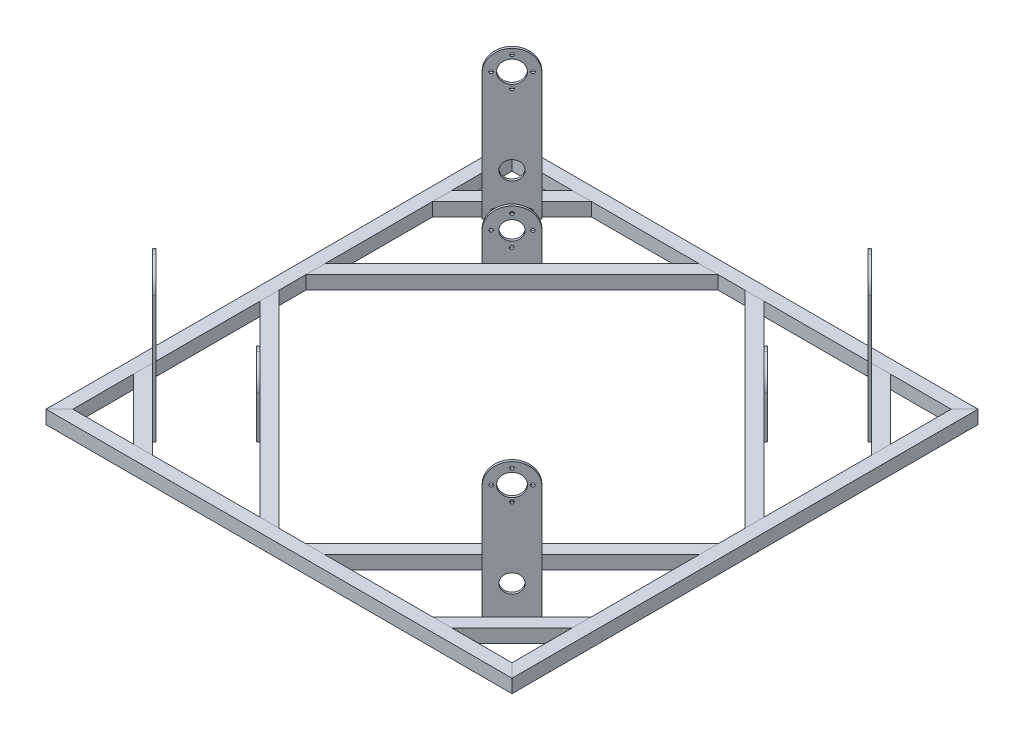
SolidWorks part; units mm, degrees
note: '?' marks a value the reader was unsure of.
material "Alumina"
material "Alumina"
material "Alumina"
material "Plain Carbon Steel"
ref_plane "Front Plane" through (0, 0, 0) normal (0, 0, 1) x (1, 0, 0)
ref_plane "Top Plane" through (0, 0, 0) normal (0, 1, 0) x (1, 0, 0)
ref_plane "Right Plane" through (0, 0, 0) normal (1, 0, 0) x (0, 0, -1)
sketch "Sketch1" plane through (0, 0, 0) normal (0, 1, 0) x (1, 0, 0)
  line L0 (0, 390) -> (0, -390) construction
  line L1 (-390, 0) -> (390, 0) construction
  circle A0 centre (0, 0) radius 390 construction
  dimension "D1" = 780
sketch3d "sketch_profile_base"
  line L0 (-149.9066, 0, 275.7716) -> (-275.7716, 0, 149.9066)
  line L1 (-275.7716, 0, -275.7716) -> (-275.7716, 0, 275.7716)
  line L2 (-275.7716, 0, -275.7716) -> (275.7716, 0, -275.7716)
  line L3 (275.7716, 0, -275.7716) -> (275.7716, 0, 275.7716)
  line L4 (-275.7716, 0, 275.7716) -> (275.7716, 0, 275.7716)
  line L5 (-275.7716, 0, -275.7716) -> (275.7716, 0, 275.7716) construction
  line L6 (275.7716, 0, -275.7716) -> (-275.7716, 0, 275.7716) construction
  line L7 (0, 0, 275.7716) -> (-275.7716, 0, 0)
  line L8 (-390, 0, 0) -> (390, 0, 0) construction
  circle A0 centre (0, 0, 0) radius 390 construction
  point P0 (0, 0, 0)
  point P8 (0, 390, 0)
  dimension "D1" = 45
  dimension "D3" = 106
other "profile_base" corner treatment miter
ref_plane "Plane1" through (-267.8341, 7.9375, -275.7716) normal (0, 0, 1) x (1, 0, 0)
sketch "Sketch12" plane through (-267.8341, 7.9375, -275.7716) normal (0, 0, 1) x (1, 0, 0)
  line L0 (-5.9375, -5.9375) -> (5.9375, -5.9375)
  line L1 (-5.9375, -5.9375) -> (-5.9375, 5.9375)
  line L2 (7.9375, 7.9375) -> (-7.9375, 7.9375)
  line L3 (5.9375, 5.9375) -> (5.9375, -5.9375)
  line L4 (-5.9375, 5.9375) -> (5.9375, 5.9375)
  line L5 (-7.9375, -7.9375) -> (-7.9375, 7.9375)
  line L6 (-7.9375, -7.9375) -> (7.9375, -7.9375)
  line L7 (7.9375, 7.9375) -> (7.9375, -7.9375)
  line L8 (0, -7.9375) -> (0, 7.9375) construction
  line L9 (0, 7.9375) -> (0, -5.9375) construction
  line L10 (0, -5.9375) -> (0, 5.9375) construction
  line L11 (-7.9375, 0) -> (-5.9375, 0) construction
  line L12 (-5.9375, 0) -> (5.9375, 0) construction
  line L13 (5.9375, 0) -> (7.9375, 0) construction
  point P6 (-7.9375, -7.9375)
  point P33 (7.9375, -7.9375)
  point P35 (-7.9375, 5.9375)
  point P36 (7.9375, 5.9375)
  point P37 (0, 0)
  point P38 (0, 0)
  dimension "D1" = 15.875
  dimension "D2" = 15.875
  dimension "D3" = 2
  dimension "D4" = 2
sketch "Sketch14" plane through (-212.8391, 0, 212.8391) normal (0.7071, 0, -0.7071) x (-0.7071, 0, -0.7071)
  line L0 (0, 0) -> (0, 175) construction
  line L1 (66.5494, 0) -> (-66.5494, 0) construction
  line L4 (-25, 0) -> (25, 0)
  line L5 (-25, 0) -> (-25, 175)
  line L6 (-25, 175) -> (25, 175)
  line L7 (25, 0) -> (25, 175)
  circle A0 centre (0, 151) radius 12.95
  circle A1 centre (0, 168.46) radius 2
  circle A2 centre (17.46, 151) radius 2
  circle A3 centre (0, 133.54) radius 2
  circle A4 centre (-17.46, 151) radius 2
  circle A5 centre (0, 7.9375) radius 3
  circle A6 centre (15, 7.9375) radius 3
  circle A7 centre (-15, 7.9375) radius 3
  circle A8 centre (0, 50) radius 11
  circle A9 centre (0, 152.66) radius 5 construction
  point P21 (0, 151)
  dimension "D2" = 25.9
  dimension "D3" = 4
  dimension "D8" = 6
  dimension "D11" = 22
  dimension "D1" = 151
  dimension "D4" = 17.46
  dimension "D6" = 175
  dimension "D7" = 50
  dimension "D9" = 15
  dimension "D10" = 7.9375
  dimension "D12" = 50
  dimension "D13" = 102.66
  dimension "D5" = 4
extrude "long_omni_mount" add sketch "Sketch14" along normal blind 3 separate body
sketch "Sketch15" plane through (-149.1111, 0, 149.1111) normal (-0.7071, 0, 0.7071) x (0.7071, 0, 0.7071)
  line L0 (0, 0) -> (0, 75) construction
  line L1 (-25, 0) -> (25, 0)
  line L2 (-25, 0) -> (-25, 75)
  line L3 (-25, 75) -> (25, 75)
  line L4 (25, 0) -> (25, 75)
  line L5 (-156.6744, 0) -> (156.6744, 0) construction
  circle A0 centre (0, 50) radius 11
  circle A1 centre (0, 67.46) radius 2
  circle A5 centre (0, 7.9375) radius 3
  circle A6 centre (15, 7.9375) radius 3
  circle A7 centre (-15, 7.9375) radius 3
  circle A8 centre (17.4791, 50.117) radius 2
  circle A9 centre (0.1361, 32.6379) radius 2
  circle A10 centre (-17.343, 49.9809) radius 2
  point P19 (0.068, 50.0489)
  point P28 (0.068, 50.0489)
  dimension "D3" = 4
  dimension "D4" = 17.46
  dimension "D2" = 22
  dimension "D7" = 6
  dimension "D1" = 50
  dimension "D5" = 75
  dimension "D6" = 50
  dimension "D8" = 15
  dimension "D9" = 7.9375
  dimension "D10" = 4
extrude "short_omni_mount" add sketch "Sketch15" along normal blind 3 separate body
fillet "fillet_short_omni_mount" radius 25 2 edges at (-132.4941, 75, 167.8495) (-167.8495, 75, 132.4941)
fillet "Fillet1" radius 25 2 edges at (-229.4562, 175, 194.1008) (-194.1008, 175, 229.4562)
ref_axis "Axis1" through (0, 183.75, 0) along (0, -1, 0)?
pattern_circular "CirPattern1" count 4 over 360 about axis through (0, 0, 0) along (0, 1, 0) of bodies 108 107 105 106
equation "\"bearing_od\"= 22mm"
equation "\"D11@Sketch14\"=\"bearing_od\""
equation "\"D2@Sketch15\"=\"bearing_od\""
equation "\"base_inner_dia\"= 780mm"
equation "\"D1@Sketch1\"=\"base_inner_dia\""
equation "\"plat_thick\"= 3mm"
equation "\"D1@long_omni_mount\"=\"plat_thick\""
equation "\"D1@short_omni_mount\"=\"plat_thick\""
equation "\"belt_center_d\"= \"D13@Sketch14\""
